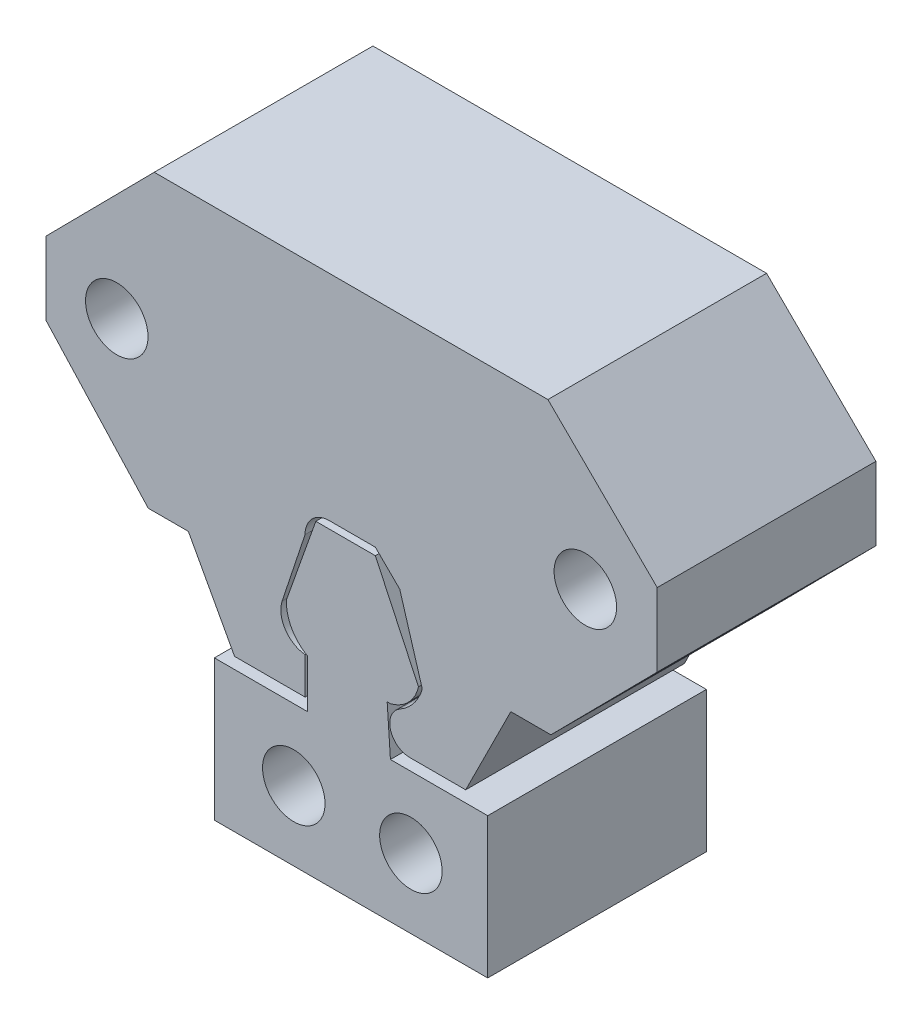
SolidWorks part; units mm, degrees
ref_plane "Front Plane" through (0, 0, 0) normal (0, 0, 1) x (1, 0, 0)
ref_plane "Top Plane" through (0, 0, 0) normal (0, 1, 0) x (1, 0, 0)
ref_plane "Right Plane" through (0, 0, 0) normal (1, 0, 0) x (0, 0, -1)
sketch "Sketch1" plane through (0, 0, 0) normal (0, 0, 1) x (1, 0, 0)
  line L0 (122.555, 198.3887) -> (200.555, 198.3887) construction
  line L1 (186.3841, 213.1351) -> (186.3841, 145.1351) construction
  line L3 (186.7465, 212.7767) -> (200.7465, 198.9271)
  line L4 (200.7465, 198.9271) -> (200.7465, 189.5559)
  line L5 (200.7465, 189.5559) -> (187.1301, 175.7916)
  line L6 (187.1301, 175.7916) -> (181.9968, 175.7916)
  line L7 (181.9968, 175.7916) -> (176.2207, 164.2339)
  line L8 (176.2207, 164.2339) -> (169.0289, 164.2339)
  line L9 (170.6634, 172.6244) -> (167.7718, 182.2703)
  line L10 (167.7718, 182.2703) -> (164.6535, 185.3551)
  line L11 (164.6535, 185.3551) -> (158.7543, 185.3551)
  line L12 (155.6512, 182.253) -> (152.7199, 173.4253)
  line L13 (154.2027, 164.2339) -> (146.6276, 164.2339)
  line L14 (146.6276, 164.2339) -> (140.7091, 175.1351)
  line L15 (155.6666, 168.9446) -> (155.6666, 164.2339)
  line L16 (155.6666, 162.7767) -> (144.0394, 162.7767)
  line L17 (144.0394, 162.7767) -> (144.0394, 144.7767)
  line L18 (144.0394, 144.7767) -> (179.0394, 144.7767)
  line L19 (179.0394, 144.7767) -> (179.0394, 162.7767)
  line L20 (179.0394, 162.7767) -> (166.582, 162.7767)
  line L21 (136.3402, 212.7767) -> (122.4906, 198.7767)
  line L22 (122.4906, 198.7767) -> (122.4906, 189.4054)
  line L23 (122.4906, 189.4054) -> (135.5757, 175.1351)
  line L24 (135.5757, 175.1351) -> (140.7091, 175.1351)
  line L25 (131.5394, 194.1351) -> (191.5394, 194.1351) construction
  line L27 (155.6666, 162.7767) -> (155.9626, 162.7767)
  line L29 (136.3402, 212.7767) -> (186.7465, 212.7767)
  line L30 (154.2027, 164.2339) -> (155.6666, 164.2339)
  line L31 (155.9626, 162.7767) -> (155.9626, 168.9446)
  line L32 (153.2635, 173.818) -> (157.026, 184.4131)
  line L33 (157.026, 184.4131) -> (164.6535, 184.4131)
  line L34 (164.6535, 184.4131) -> (170.1746, 172.6244)
  line L35 (166.582, 168.9633) -> (166.1647, 168.9633)
  line L36 (166.1647, 168.9633) -> (166.582, 162.7767)
  circle A0 centre (131.5394, 194.1351) radius 4
  arc A1 (169.0289, 164.2339) -> (167.7718, 168.9633) centre (169.0289, 166.7656) cw
  arc A2 (167.7718, 168.9633) -> (170.6634, 172.6244) centre (164.6707, 174.385) ccw
  arc A3 (158.7543, 185.3551) -> (155.6512, 182.253) centre (158.7543, 182.252) ccw
  arc A4 (152.7199, 173.4253) -> (155.6666, 168.9446) centre (155.9626, 172.3486) ccw
  circle A6 centre (191.5394, 194.1351) radius 4
  circle A7 centre (154.2027, 153.6868) radius 4
  circle A8 centre (169.2027, 153.6868) radius 4
  arc A9 (155.9626, 168.9446) -> (153.2635, 173.818) centre (158.6151, 173.5978) cw
  arc A10 (170.1746, 172.6244) -> (166.582, 168.9633) centre (165.3933, 173.723) cw
  point P42 (161.5394, 194.1351)
  point P43 (161.5394, 144.7767)
  dimension "D8" = 8
  dimension "D4" = 9.3712
  dimension "D5" = 19.3613
  dimension "D7" = 60
  dimension "D9" = 35
  dimension "D10" = 18
  dimension "D11" = 15
  dimension "D2" = 68
extrude "Boss-Extrude1" add sketch "Sketch1" along normal blind 28
